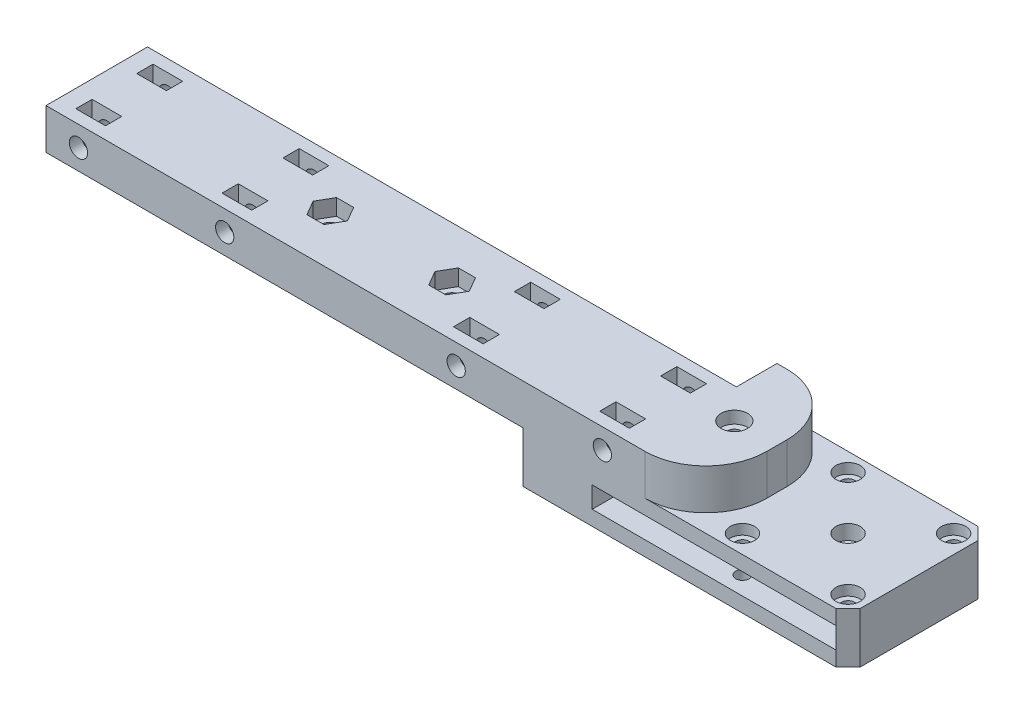
SolidWorks part; units mm, degrees
ref_plane "Front Plane" through (0, 0, 0) normal (0, 0, 1) x (1, 0, 0)
ref_plane "Top Plane" through (0, 0, 0) normal (0, 1, 0) x (1, 0, 0)
ref_plane "Right Plane" through (0, 0, 0) normal (1, 0, 0) x (0, 0, -1)
sketch "Sketch1" plane through (0, 0, 0) normal (0, 1, 0) x (1, 0, 0)
  line L7 (0, 0) -> (145, 0)
  line L8 (0, 0) -> (0, 25)
  line L9 (0, 25) -> (145, 25)
  line L10 (145, 0) -> (145, 25)
  dimension "D1" = 25
  dimension "D3" = 145
extrude "Boss-Extrude1" add sketch "Sketch1" along normal blind 10 contours L7 L10 L9 region at (72.5, 0, -12.5)
sketch "Sketch2" plane through (0, 10, 0) normal (0, 1, 0) x (1, 0, 0)
  line L5 (145, 0) -> (162.5, 0)
  line L6 (145, 0) -> (145, 35)
  line L7 (145, 35) -> (162.5, 35)
  line L8 (162.5, 0) -> (162.5, 35)
  dimension "D1" = 17.5
  dimension "D2" = 35
extrude "Boss-Extrude2" add sketch "Sketch2" against normal blind 10
sketch "Sketch4" plane through (0, 0, 0) normal (0, -1, 0) x (1, 0, 0)
  line L0 (162.5, -35) -> (197.5, -35) construction
  line L1 (162.5, 0) -> (117.5, 0) construction
  line L2 (0, 0) -> (162.5, 0) construction
  line L4 (117.5, 0) -> (197.5, 0)
  line L5 (117.5, 0) -> (117.5, -35)
  line L6 (117.5, -35) -> (197.5, -35)
  line L7 (197.5, 0) -> (197.5, -35)
  dimension "D1" = 35
  dimension "D2" = 45
extrude "Boss-Extrude3" add sketch "Sketch4" along normal blind 12.5
sketch "Sketch8" plane through (0, 0, -25) normal (0, 0, -1) x (-1, 0, 0)
  line L0 (-145, 5) -> (0, 5) construction
  line L1 (-145, 10) -> (-145, 0) construction
  line L2 (0, 10) -> (0, 0) construction
  line L3 (-72.5, 10) -> (-72.5, 0) construction
  line L4 (0, 10) -> (-145, 10) construction
  line L5 (0, 0) -> (-117.5, 0) construction
  circle A0 centre (-137, 5) radius 2.25
  circle A1 centre (-101, 5) radius 2.25
  circle A2 centre (-44, 5) radius 2.25
  circle A3 centre (-8, 5) radius 2.25
  dimension "D1" = 8
  dimension "D2" = 4.5
  dimension "D4" = 36
  dimension "D3" = 2
extrude "Cut-Extrude5" cut sketch "Sketch8" against normal through all
sketch "Sketch9" plane through (0, 10, 0) normal (0, 1, 0) x (1, 0, 0)
  line L0 (145, 25) -> (145, 0) construction
  line L1 (0, 0) -> (162.5, 0) construction
  line L2 (145, 12.5) -> (0, 12.5) construction
  line L3 (0, 0) -> (0, 25) construction
  line L4 (72.5, 25) -> (72.5, 0) construction
  line L5 (0, 25) -> (145, 25) construction
  line L6 (137, 0) -> (137, 25) construction
  line L7 (140.65, 22) -> (133.35, 22)
  line L8 (140.65, 7) -> (133.35, 7)
  line L9 (140.65, 7) -> (140.65, 3)
  line L10 (140.65, 3) -> (133.35, 3)
  line L11 (133.35, 7) -> (133.35, 3)
  line L12 (140.65, 7) -> (133.35, 3) construction
  line L13 (140.65, 3) -> (133.35, 7) construction
  line L14 (133.35, 18) -> (133.35, 22)
  line L15 (140.65, 18) -> (133.35, 18)
  line L16 (140.65, 18) -> (140.65, 22)
  line L17 (104.65, 7) -> (104.65, 3)
  line L18 (104.65, 7) -> (97.35, 7)
  line L19 (97.35, 7) -> (97.35, 3)
  line L20 (104.65, 3) -> (97.35, 3)
  line L21 (104.65, 22) -> (97.35, 22)
  line L22 (97.35, 18) -> (97.35, 22)
  line L23 (104.65, 18) -> (97.35, 18)
  line L24 (104.65, 18) -> (104.65, 22)
  line L25 (4.35, 18) -> (4.35, 22)
  line L26 (4.35, 18) -> (11.65, 18)
  line L27 (11.65, 18) -> (11.65, 22)
  line L28 (4.35, 22) -> (11.65, 22)
  line L29 (40.35, 18) -> (40.35, 22)
  line L30 (40.35, 18) -> (47.65, 18)
  line L31 (47.65, 18) -> (47.65, 22)
  line L32 (40.35, 22) -> (47.65, 22)
  line L33 (40.35, 7) -> (47.65, 7)
  line L34 (47.65, 7) -> (47.65, 3)
  line L35 (40.35, 3) -> (47.65, 3)
  line L36 (40.35, 7) -> (40.35, 3)
  line L37 (4.35, 3) -> (11.65, 3)
  line L38 (11.65, 7) -> (11.65, 3)
  line L39 (4.35, 7) -> (11.65, 7)
  line L40 (4.35, 7) -> (4.35, 3)
  point P15 (137, 5)
  dimension "D1" = 8
  dimension "D2" = 5
  dimension "D3" = 7.3
  dimension "D4" = 4
  dimension "D6" = 36
  dimension "D5" = 2
extrude "Cut-Extrude6" cut sketch "Sketch9" against normal up to surface (10 mm away) up to face at (58.75, 0, -12.5)
sketch "Sketch10" plane through (0, 0, 0) normal (0, 1, 0) x (1, 0, 0)
  line L0 (197.5, 17.5) -> (162.5, 17.5) construction
  line L1 (197.5, 35) -> (197.5, 0) construction
  line L2 (162.5, 0) -> (162.5, 35) construction
  line L3 (180, 0) -> (180, 35) construction
  line L6 (197.5, 0) -> (162.5, 0) construction
  line L7 (162.5, 35) -> (197.5, 35) construction
  circle A1 centre (180, 17.5) radius 3
  circle A2 centre (193, 4.5) radius 1.65
  circle A3 centre (167, 4.5) radius 1.65
  circle A4 centre (167, 30.5) radius 1.65
  circle A5 centre (193, 30.5) radius 1.65
  dimension "D1" = 6
  dimension "D2" = 3.3
  dimension "D3" = 13
  dimension "D4" = 13
  dimension "D5" = 17.5
extrude "Cut-Extrude7" cut sketch "Sketch10" against normal up to next
chamfer "Chamfer1" distance 3 angle 45 2 edges at (197.5, -6.25, -35) (197.5, -6.25, 0)
fillet "Fillet1" radius 15 2 edges at (162.5, 5, 0) (162.5, 5, -35)
sketch "Sketch14" plane through (0, -12.5, 0) normal (0, -1, 0) x (1, 0, 0)
  circle A0 centre (180, -17.5) radius 11.25
  dimension "D1" = 22.5
extrude "Cut-Extrude11" cut sketch "Sketch14" against normal blind 2.5
sketch "Sketch15" plane through (0, 0, 0) normal (0, 1, 0) x (1, 0, 0)
  line L0 (167, 30.5) -> (193, 30.5) construction
  line L1 (167, 4.5) -> (193, 4.5) construction
  line L2 (180, 30.5) -> (180, 4.5) construction
  line L3 (197.5, 17.5) -> (180, 17.5) construction
  line L4 (197.5, 32) -> (197.5, 3) construction
  circle A0 centre (167, 30.5) radius 3
  circle A1 centre (193, 30.5) radius 3
  circle A2 centre (193, 4.5) radius 3
  circle A3 centre (167, 4.5) radius 3
  dimension "D1" = 6
extrude "Cut-Extrude12" cut sketch "Sketch15" against normal blind 2.5
sketch "Sketch16" plane through (0, 10, 0) normal (0, 1, 0) x (1, 0, 0)
  line L0 (52, 25) -> (52, 0) construction
  line L1 (0, 25) -> (145, 25) construction
  line L2 (0, 0) -> (147.5, 0) construction
  line L3 (0, 0) -> (0, 25) construction
  line L4 (93, 25) -> (93, 0) construction
  line L5 (52, 12.5) -> (93, 12.5) construction
  line L6 (72.5, 12.5) -> (72.5, 0) construction
  circle A0 centre (57.5, 12.5) radius 2.25
  circle A1 centre (87.5, 12.5) radius 2.25
  dimension "D3" = 4.5
  dimension "D4" = 15
  dimension "D5" = 30
  dimension "D6" = 57.5
  dimension "D1" = 52
  dimension "D2" = 93
extrude "Cut-Extrude13" cut sketch "Sketch16" against normal up to next
sketch "Sketch18" plane through (0, 10, 0) normal (0, 1, 0) x (1, 0, 0)
  line L0 (87.5, 12.5) -> (57.5, 12.5) construction
  line L1 (72.5, 12.5) -> (72.5, 0) construction
  line L2 (83.2853, 12.5) -> (85.3927, 8.85)
  line L3 (85.3927, 8.85) -> (89.6073, 8.85)
  line L4 (89.6073, 8.85) -> (91.7147, 12.5)
  line L5 (91.7147, 12.5) -> (89.6073, 16.15)
  line L6 (89.6073, 16.15) -> (85.3927, 16.15)
  line L7 (85.3927, 16.15) -> (83.2853, 12.5)
  line L8 (0, 0) -> (147.5, 0) construction
  line L9 (59.6073, 16.15) -> (61.7147, 12.5)
  line L10 (55.3927, 16.15) -> (59.6073, 16.15)
  line L11 (53.2853, 12.5) -> (55.3927, 16.15)
  line L12 (55.3927, 8.85) -> (53.2853, 12.5)
  line L13 (59.6073, 8.85) -> (55.3927, 8.85)
  line L14 (61.7147, 12.5) -> (59.6073, 8.85)
  circle A0 centre (87.5, 12.5) radius 3.65 construction
  dimension "D1" = 7.3
  dimension "D2" = 3.65
extrude "Cut-Extrude15" cut sketch "Sketch18" against normal blind 4
sketch "Sketch19" plane through (0, 0, 0) normal (0, 0, 1) x (1, 0, 0)
  line L0 (194.5, -6.25) -> (117.5, -6.25) construction
  line L1 (194.5, -12.5) -> (194.5, 0) construction
  line L2 (117.5, -12.5) -> (117.5, 0) construction
  line L3 (197.5, -12.5) -> (197.5, 0) construction
  line L4 (134.5, -8.85) -> (194.5, -8.85)
  line L5 (134.5, -8.85) -> (134.5, -3.65)
  line L6 (134.5, -3.65) -> (194.5, -3.65)
  line L7 (194.5, -8.85) -> (194.5, -3.65)
  line L8 (134.5, -8.85) -> (194.5, -3.65) construction
  line L9 (134.5, -3.65) -> (194.5, -8.85) construction
  line L10 (117.5, -12.5) -> (117.5, 0) construction
  line L11 (117.5, -12.5) -> (194.5, -12.5) construction
  point P6 (164.5, -6.25)
  dimension "D1" = 60
  dimension "D2" = 5.2
  dimension "D3" = 3
  dimension "D4" = 47
  dimension "D5" = 3.65
extrude "Cut-Extrude16" cut sketch "Sketch19" against normal up to next
sketch "Sketch20" plane through (0, 10, 0) normal (0, 1, 0) x (1, 0, 0)
  line L0 (180, 17.5) -> (152, 17.5) construction
  line L1 (147.5, 35) -> (194.5, 35) construction
  circle A0 centre (152, 17.5) radius 1.75
  dimension "D2" = 3.5
  dimension "D4" = 17.5
  dimension "D1" = 28
  dimension "D3" = 152
extrude "Cut-Extrude17" cut sketch "Sketch20" against normal through all
sketch "Sketch21" plane through (0, -12.5, 0) normal (0, -1, 0) x (1, 0, 0)
  line L1 (140, -29.5) -> (164, -29.5)
  line L2 (140, -29.5) -> (140, -5.5)
  line L3 (140, -5.5) -> (164, -5.5)
  line L4 (164, -29.5) -> (164, -5.5)
  line L5 (140, -29.5) -> (164, -5.5) construction
  line L6 (140, -5.5) -> (164, -29.5) construction
  point P0 (152, -17.5)
  dimension "D1" = 24
  dimension "D2" = 24
extrude "Cut-Extrude18" cut sketch "Sketch21" against normal blind 2
sketch "Sketch22" plane through (0, -10.5, 0) normal (0, -1, 0) x (1, 0, 0)
  line L0 (152, -5.5) -> (152, -29.5) construction
  line L1 (164, -5.5) -> (140, -5.5) construction
  line L2 (140, -29.5) -> (164, -29.5) construction
  line L3 (140, -17.5) -> (164, -17.5) construction
  line L4 (140, -5.5) -> (140, -29.5) construction
  line L5 (164, -29.5) -> (164, -5.5) construction
  line L7 (144, -22) -> (160, -22)
  line L8 (144, -22) -> (144, -13)
  line L9 (144, -13) -> (160, -13)
  line L10 (160, -22) -> (160, -13)
  line L11 (144, -22) -> (160, -13) construction
  line L12 (144, -13) -> (160, -22) construction
  circle A0 centre (144, -9.5) radius 1.65
  circle A1 centre (160, -9.5) radius 1.65
  circle A2 centre (160, -25.5) radius 1.65
  circle A3 centre (144, -25.5) radius 1.65
  point P20 (152, -17.5)
  dimension "D1" = 8
  dimension "D2" = 8
  dimension "D3" = 3.3
  dimension "D4" = 9
  dimension "D5" = 16
extrude "Cut-Extrude19" cut sketch "Sketch22" against normal up to next
sketch "Sketch23" plane through (0, 10, 0) normal (0, 1, 0) x (1, 0, 0)
  circle A0 centre (152, 17.5) radius 3.25
  dimension "D1" = 6.5
extrude "Cut-Extrude20" cut sketch "Sketch23" against normal blind 3
sketch "Sketch24" plane through (0, -3.65, 0) normal (0, -1, 0) x (1, 0, 0)
  circle A0 centre (152, -17.5) radius 3.25
  dimension "D1" = 6.5
extrude "Cut-Extrude21" cut sketch "Sketch24" against normal blind 3
